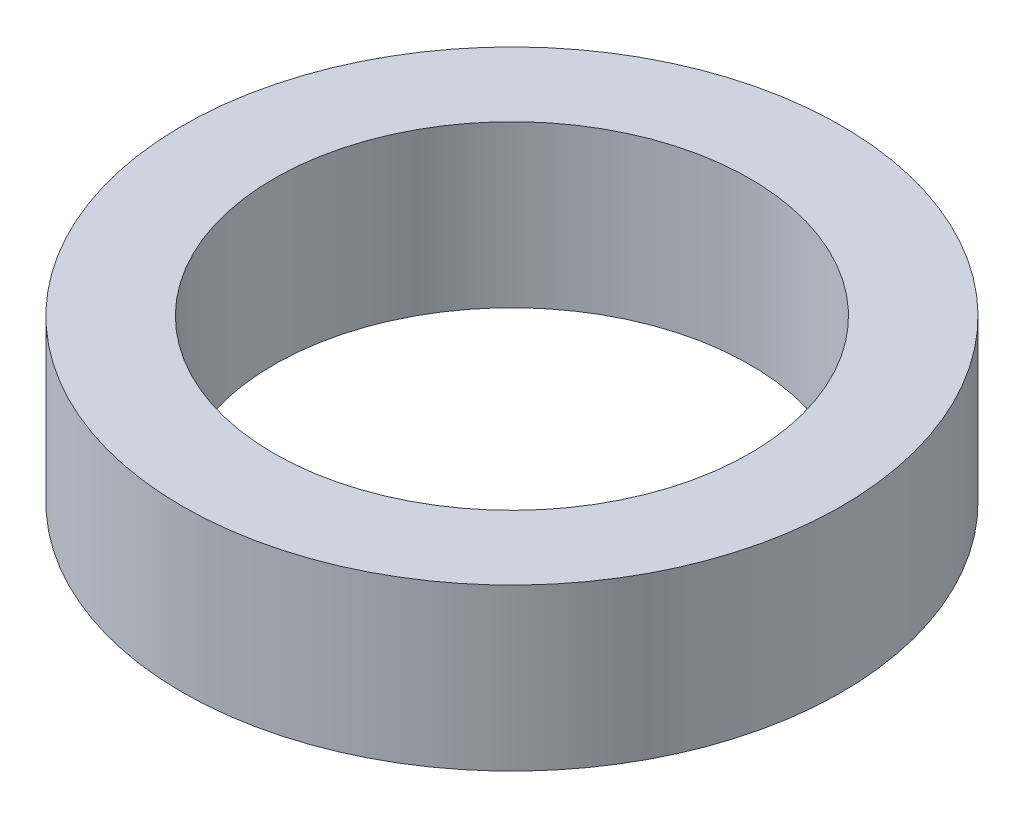
SolidWorks part; units mm, degrees
ref_plane "Front Plane" through (0, 0, 0) normal (0, 0, 1) x (1, 0, 0)
ref_plane "Top Plane" through (0, 0, 0) normal (0, 1, 0) x (1, 0, 0)
ref_plane "Right Plane" through (0, 0, 0) normal (1, 0, 0) x (0, 0, -1)
sketch "Sketch1" plane through (0, 0, 0) normal (0, 1, 0) x (1, 0, 0)
  circle A0 centre (0, 0) radius 45
  dimension "FLANGE_OD" = 90
extrude "Boss-Extrude1" add sketch "Sketch1" along normal blind 22
sketch "Sketch2" plane through (0, 0, 0) normal (0, 1, 0) x (1, 0, 0)
  circle A0 centre (0, 0) radius 32.5
  dimension "BORE_D" = 65
extrude "Cut-Extrude1" cut sketch "Sketch2" along normal through all
sketch "Sketch3" plane through (0, 22, 0) normal (0, 1, 0) x (1, 0, 0)
  circle A0 centre (0, 0) radius 19.0893 construction
  circle A1 centre (-19.0893, 0) radius 1.6911
  dimension "BOLT_D" = 3.3823
  dimension "BOLT_PCD" = 38.1786
extrude "Cut-Extrude2" cut sketch "Sketch3" against normal blind 19.2033 rebuild error yes
pattern_circular "CirPattern1" count 4 over 360 rebuild error yes
